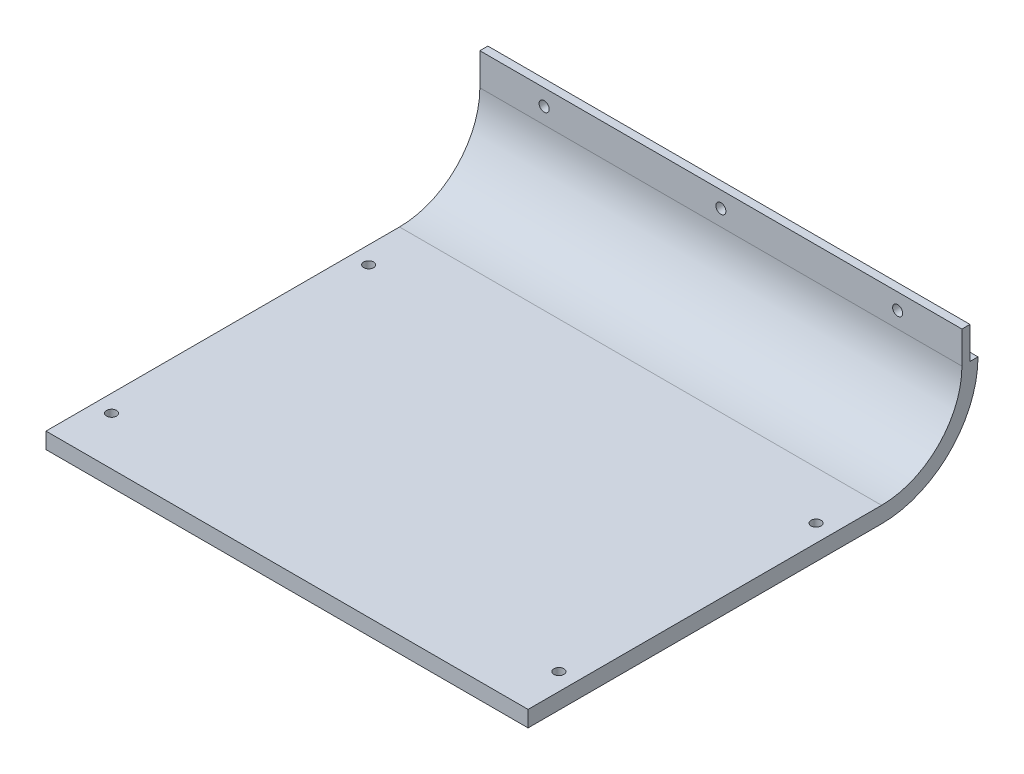
SolidWorks part; units mm, degrees
material "6061-T6 Aluminum"
ref_plane "Front Plane" through (0, 0, 0) normal (0, 0, 1) x (1, 0, 0)
ref_plane "Top Plane" through (0, 0, 0) normal (0, 1, 0) x (1, 0, 0)
ref_plane "Right Plane" through (0, 0, 0) normal (1, 0, 0) x (0, 0, -1)
sketch "Sketch1" plane through (0, 0, 0) normal (1, 0, 0) x (0, 0, -1)
  line L0 (-139.7, 0) -> (139.7, 0)
  line L5 (139.7, 0) -> (139.7, 12.7) construction
  line L7 (-139.7, 12.7) -> (139.7, 12.7)
  line L9 (-139.7, 0) -> (-139.7, 12.7)
  line L12 (139.7, 0) -> (139.7, 152.4) construction
  line L13 (0.6365, 139.0796) -> (-139.7417, 139.9778) construction
  line L14 (-12.6991, 151.8652) -> (-139.6605, 152.6775) construction
  line L15 (203.2, 76.2) -> (215.9, 76.2)
  arc A2 (139.7, 0) -> (-12.6991, 151.8652) centre (139.7, 152.4) ccw construction
  arc A3 (139.7, 12.7) -> (0.6365, 139.0796) centre (139.7, 152.4) ccw construction
  circle A5 centre (139.7, 76.2) radius 76.2 construction
  arc A6 (215.9, 76.2) -> (139.7, 0) centre (139.7, 76.2) cw
  circle A7 centre (139.7, 76.2) radius 63.5 construction
  arc A8 (203.2, 76.2) -> (139.7, 12.7) centre (139.7, 76.2) cw
  point P3 (0, 0)
  dimension "D1" = 152.4
  dimension "D2" = 12.7
  dimension "D4" = 127
  dimension "D6" = 12.7
  dimension "D3" = 12.7
  dimension "D5" = 12.7
  dimension "D7" = 355.6
extrude "Boss-Extrude1" add sketch "Sketch1" along normal blind 190.5 and the other way blind 190.5
sketch "Sketch2" plane through (0, 76.2, 0) normal (0, 1, 0) x (1, 0, 0)
  line L0 (-190.5, 215.9) -> (-190.5, 203.2) construction
  line L1 (-190.5, 209.55) -> (190.5, 209.55)
  line L2 (-190.5, 209.55) -> (-190.5, 203.2)
  line L3 (-190.5, 203.2) -> (190.5, 203.2)
  line L4 (190.5, 209.55) -> (190.5, 203.2)
extrude "Boss-Extrude2" add sketch "Sketch2" along normal blind 25.4
sketch "Sketch3" plane through (0, 0, -209.55) normal (0, 0, -1) x (-1, 0, 0)
  line L0 (-190.5, 88.9) -> (190.5, 88.9) construction
  line L1 (-190.5, 101.6) -> (-190.5, 76.2) construction
  line L2 (190.5, 101.6) -> (190.5, 76.2) construction
  line L3 (-139.7, 101.6) -> (-139.7, 76.2) construction
  line L4 (-190.5, 101.6) -> (190.5, 101.6) construction
  line L5 (-190.5, 76.2) -> (190.5, 76.2) construction
  line L6 (0, 101.6) -> (0, 76.2) construction
  line L7 (190.5, 76.2) -> (-190.5, 76.2) construction
  line L8 (139.7, 101.6) -> (139.7, 76.2) construction
  circle A0 centre (-139.7, 88.9) radius 3.9687
  circle A1 centre (139.7, 88.9) radius 3.9687
  circle A2 centre (0, 88.9) radius 3.9687
  dimension "D3" = 7.9375
  dimension "D1" = 139.7
  dimension "D2" = 139.7
extrude "Cut-Extrude1" cut sketch "Sketch3" against normal blind 25.4
sketch "Sketch4" plane through (0, 12.7, 0) normal (0, 1, 0) x (1, 0, 0)
  line L0 (0, -139.7) -> (0, -101.6) construction
  line L1 (-190.5, -139.7) -> (190.5, -139.7) construction
  line L2 (0, -101.6) -> (0, 0) construction
  line L3 (0, 0) -> (0, 101.6) construction
  line L4 (0, 101.6) -> (0, 139.7) construction
  line L5 (-190.5, 139.7) -> (190.5, 139.7) construction
  line L6 (-176.784, 101.6) -> (176.784, 101.6) construction
  line L7 (-176.784, 0) -> (176.784, 0) construction
  line L8 (-176.784, -101.6) -> (176.784, -101.6) construction
  line L10 (190.5, 139.7) -> (190.5, -139.7) construction
  circle A0 centre (176.784, -101.6) radius 3.937
  circle A2 centre (176.784, 101.6) radius 3.937
  circle A3 centre (-176.784, -101.6) radius 3.937
  circle A5 centre (-176.784, 101.6) radius 3.937
  point P12 (0, 101.6)
  point P15 (0, 0)
  point P19 (0, -101.6)
  dimension "D3" = 7.874
  dimension "D1" = 203.2
  dimension "D2" = 13.716
extrude "Cut-Extrude2" cut sketch "Sketch4" against normal through all
